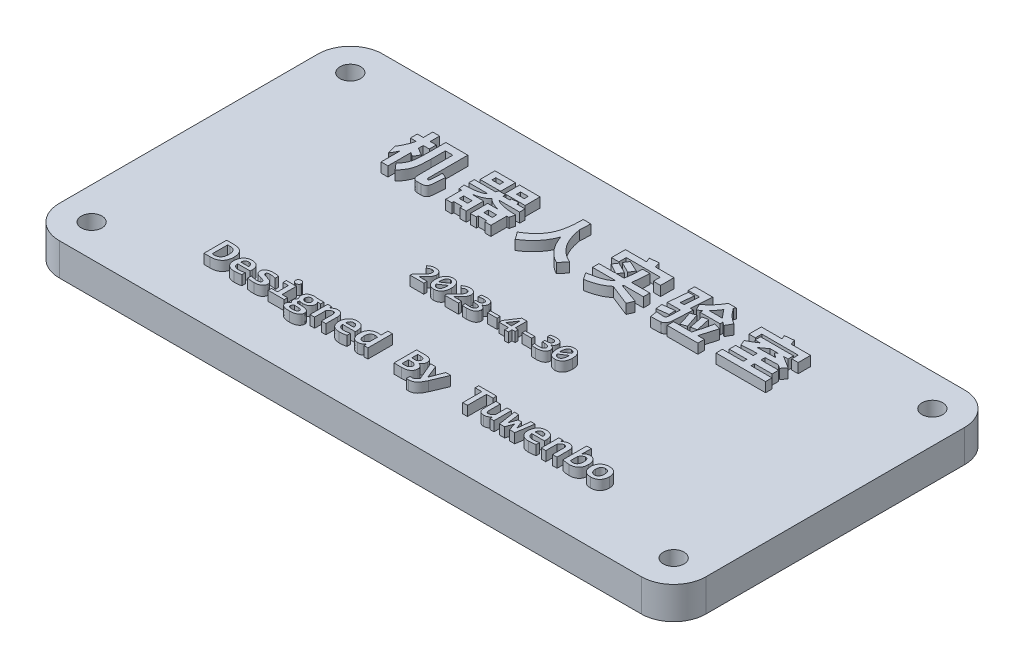
SolidWorks part; units mm, degrees
ref_plane "前视基准面" through (0, 0, 0) normal (0, 0, 1) x (1, 0, 0)
ref_plane "上视基准面" through (0, 0, 0) normal (0, 1, 0) x (1, 0, 0)
ref_plane "右视基准面" through (0, 0, 0) normal (1, 0, 0) x (0, 0, -1)
sketch "草图1" plane through (0, 0, 0) normal (0, 1, 0) x (1, 0, 0)
  line L1 (-50, 25) -> (50, 25)
  line L2 (-50, 25) -> (-50, -25)
  line L3 (-50, -25) -> (50, -25)
  line L4 (50, 25) -> (50, -25)
  line L5 (-50, 25) -> (50, -25) construction
  line L6 (-50, -25) -> (50, 25) construction
  point P0 (0, 0)
  dimension "D1" = 100
  dimension "D2" = 50
extrude "凸台-拉伸1" add sketch "草图1" along normal blind 5
sketch "草图3" plane through (0, 5, 0) normal (0, 1, 0) x (1, 0, 0)
  line L0 (0, 0) -> (0, 22.5181) construction
  line L1 (0, 0) -> (57.3253, 0) construction
  circle A0 centre (-45, 20) radius 1.6
  circle A1 centre (45, 20) radius 1.6
  circle A2 centre (45, -20) radius 1.6
  circle A3 centre (-45, -20) radius 1.6
  dimension "D1" = 3.2
  dimension "D2" = 90
  dimension "D3" = 40
extrude "切除-拉伸3" cut sketch "草图3" against normal through all
sketch "草图4" plane through (0, 5, 0) normal (0, 1, 0) x (1, 0, 0)
  line L0 (-50, -17) -> (50, -17) construction
  line L1 (-50, 25) -> (-50, -25) construction
  line L2 (50, -25) -> (50, 25) construction
  line L3 (-50, 10) -> (50, 10) construction
  line L4 (-50, -25) -> (50, -25) construction
  line L5 (50, 25) -> (-50, 25) construction
  line L6 (-50, -4) -> (50, -4) construction
  text T0 "<b>Designed By Tuwenbo</b>" font "Consolas" height 3.5
  text T1 "<b>2023-4-30</b>" font "Consolas" height in points 11
  text T2 "<b>机器人实验室</b>" font "微软雅黑" height in points 22
  dimension "D1" = 8
  dimension "D2" = 15
  dimension "D3" = 21
fillet "圆角1" radius 5 4 edges at (50, 2.5, -25) (50, 2.5, 25) (-50, 2.5, 25) (-50, 2.5, -25)
extrude "凸台-拉伸2" add sketch "草图4" along normal blind 1.5
